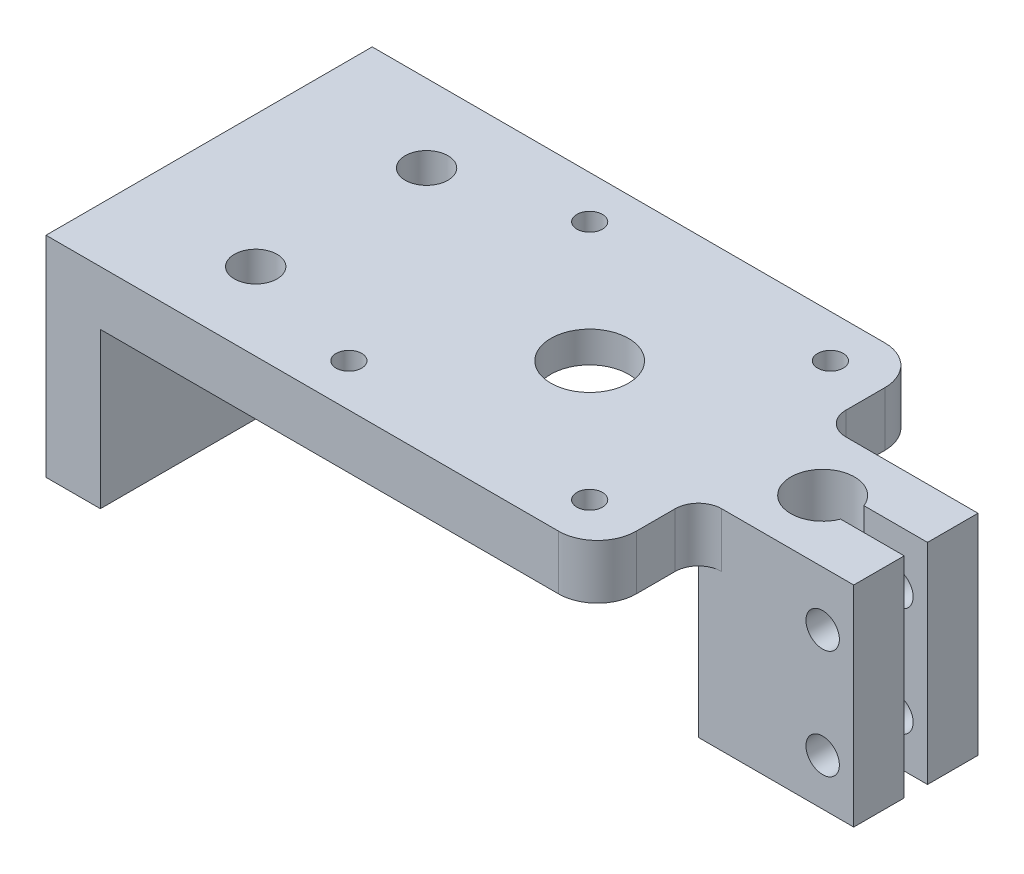
SolidWorks part; units mm, degrees
material "ABS PC"
ref_plane "Front Plane" through (0, 0, 0) normal (0, 0, 1) x (1, 0, 0)
ref_plane "Top Plane" through (0, 0, 0) normal (0, 1, 0) x (1, 0, 0)
ref_plane "Right Plane" through (0, 0, 0) normal (1, 0, 0) x (0, 0, -1)
sketch "Sketch1" plane through (0, 0, 0) normal (0, 1, 0) x (1, 0, 0)
  line L1 (-32, -21) -> (32, -21)
  line L2 (-32, -21) -> (-32, 21)
  line L3 (-32, 21) -> (32, 21)
  line L4 (32, -21) -> (32, 21)
  line L5 (-32, -21) -> (32, 21) construction
  line L6 (-32, 21) -> (32, -21) construction
  point P0 (0, 0)
  dimension "D1" = 64
  dimension "D2" = 42
extrude "Boss-Extrude1" add sketch "Sketch1" along normal blind 7 contours L3 L4 L1 L2
sketch "Sketch11" plane through (0, 0, 0) normal (0, 1, 0) x (1, 0, 0)
  line L0 (32, -8) -> (32, 8)
  line L1 (32, -8) -> (52, -8)
  line L2 (32, 8) -> (52, 8)
  line L3 (52, -8) -> (52, 8)
  line L4 (32, -21) -> (32, 21) construction
  line L5 (52, 0) -> (32, 0) construction
  dimension "D1" = 20
  dimension "D2" = 16
extrude "Boss-Extrude3" add sketch "Sketch11" along normal blind 7 and the other way blind 20
sketch "Sketch3" plane through (0, 0, 0) normal (0, 1, 0) x (1, 0, 0)
  circle A0 centre (10, 0) radius 12
  dimension "D1" = 24
extrude "Cut-Extrude2" cut sketch "Sketch3" along normal blind 3
sketch "Sketch2" plane through (0, 7, 0) normal (0, 1, 0) x (1, 0, 0)
  circle A0 centre (40, 0) radius 4.1
  dimension "D1" = 8.2
  dimension "D2" = 40
extrude "Cut-Extrude1" cut sketch "Sketch2" against normal through all
sketch "Sketch4" plane through (0, 7, 0) normal (0, 1, 0) x (1, 0, 0)
  line L0 (-32, -21) -> (-32, 21) construction
  line L1 (-32, 21) -> (32, 21) construction
  line L2 (-32, -21) -> (32, -21) construction
  circle A0 centre (-22, 11) radius 2.75
  circle A1 centre (-22, -11) radius 2.75
  dimension "D1" = 5.5
  dimension "D4" = 5.5
  dimension "D2" = 10
  dimension "D3" = 10
  dimension "D5" = 10
  dimension "D6" = 10
extrude "Cut-Extrude3" cut sketch "Sketch4" against normal through all
sketch "Sketch7" plane through (0, 7, 0) normal (0, 1, 0) x (1, 0, 0)
  circle A0 centre (-5.5, 15.5) radius 1.65
  circle A1 centre (25.5, 15.5) radius 1.65
  circle A2 centre (25.5, -15.5) radius 1.65
  circle A3 centre (-5.5, -15.5) radius 1.65
  dimension "D1" = 3.3
  dimension "D2" = 3.3
  dimension "D3" = 3.3
  dimension "D4" = 3.3
extrude "Cut-Extrude5" cut sketch "Sketch7" against normal through all
sketch "Sketch8" plane through (-32, 0, 0) normal (-1, 0, 0) x (0, 0, 1)
  line L1 (-21, 7) -> (21, 7)
  line L2 (-21, 7) -> (-21, -20)
  line L3 (-21, -20) -> (21, -20)
  line L4 (21, 7) -> (21, -20)
  line L5 (21, 7) -> (21, 0) construction
  dimension "D1" = 27
extrude "Boss-Extrude2" add sketch "Sketch8" along normal blind 7
sketch "Sketch9" plane through (-39, 0, 0) normal (-1, 0, 0) x (0, 0, 1)
  line L0 (-21, -20) -> (21, -20) construction
  line L1 (0, 7) -> (0, -20) construction
  line L2 (21, 7) -> (-21, 7) construction
  circle A0 centre (0, -10) radius 2.7
  dimension "D2" = 5.4
  dimension "D1" = 10
extrude "Cut-Extrude6" cut sketch "Sketch9" against normal blind 13 and the other way through all
sketch "Sketch10" plane through (0, 7, 0) normal (0, 1, 0) x (1, 0, 0)
  circle A0 centre (10, 0) radius 5
  dimension "D1" = 10
extrude "Cut-Extrude7" cut sketch "Sketch10" against normal blind 20
sketch "Sketch15" plane through (0, 0, -8) normal (0, 0, -1) x (-1, 0, 0)
  line L0 (-52, -20) -> (-52, 7) construction
  line L1 (-52, 7) -> (-32, 7) construction
  circle A0 centre (-48, 0) radius 2.15
  circle A1 centre (-48, -14) radius 2.15
  dimension "D1" = 4.3
  dimension "D2" = 4
  dimension "D3" = 7
  dimension "D4" = 14
extrude "Cut-Extrude8" cut sketch "Sketch15" against normal blind 22
sketch "Sketch16" plane through (0, 7, 0) normal (0, 1, 0) x (1, 0, 0)
  line L0 (52, -8) -> (52, 8) construction
  line L1 (38, -1.5) -> (52, -1.5)
  line L2 (38, -1.5) -> (38, 1.5)
  line L3 (38, 1.5) -> (52, 1.5)
  line L4 (52, -1.5) -> (52, 1.5)
  line L5 (38, 0) -> (52, 0) construction
  dimension "D1" = 14
  dimension "D2" = 3
extrude "Cut-Extrude9" cut sketch "Sketch16" against normal through all
fillet "Fillet1" radius 3 2 edges at (32, 3.5, 8) (32, 3.5, -8)
fillet "Fillet2" radius 5 2 edges at (32, 3.5, -21) (32, 3.5, 21)
